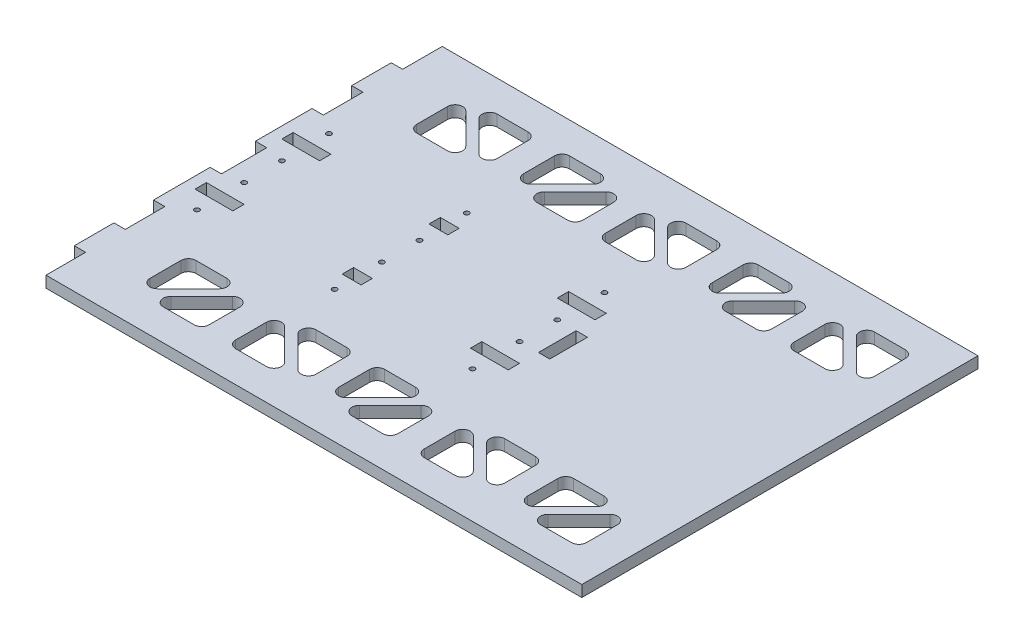
SolidWorks part; units mm, degrees
material "Balsa"
ref_plane "Front Plane" through (0, 0, 0) normal (0, 0, 1) x (1, 0, 0)
ref_plane "Top Plane" through (0, 0, 0) normal (0, 1, 0) x (1, 0, 0)
ref_plane "Right Plane" through (0, 0, 0) normal (1, 0, 0) x (0, 0, -1)
sketch "Sketch1" plane through (0, 0, 0) normal (0, 1, 0) x (1, 0, 0)
  line L0 (0, 0) -> (0, 105) construction
  line L1 (-145, 105) -> (145, 105)
  line L2 (-145, 105) -> (-145, -105)
  line L3 (-145, -105) -> (145, -105)
  line L4 (145, 105) -> (145, -105)
  line L5 (0, 0) -> (145, 0) construction
  dimension "D1" = 290
  dimension "D2" = 210
extrude "Boss-Extrude1" add sketch "Sketch1" along normal blind 6
sketch "Sketch2" plane through (0, 6, 0) normal (0, 1, 0) x (1, 0, 0)
  line L0 (-145, 105) -> (-145, -105) construction
  line L1 (145, 105) -> (-145, 105) construction
  line L2 (-145, 84) -> (-139, 84)
  line L3 (-145, 84) -> (-145, 105)
  line L4 (-145, 105) -> (-139, 105)
  line L6 (-139, 84) -> (-139, 105)
  line L7 (-145, -12) -> (-145, 0)
  line L8 (-145, 63) -> (-139, 63)
  line L9 (-145, 63) -> (-145, 42)
  line L10 (0, 0) -> (-139, 0) construction
  line L11 (-145, 42) -> (-139, 42)
  line L12 (-139, 63) -> (-139, 42)
  line L13 (-145, 12) -> (-139, 12)
  line L14 (-145, 12) -> (-145, 0)
  line L16 (-139, 12) -> (-139, -12)
  line L17 (-145, -12) -> (-139, -12)
  line L18 (-139, -63) -> (-139, -42)
  line L19 (-145, -42) -> (-139, -42)
  line L20 (-145, -63) -> (-145, -42)
  line L21 (-145, -63) -> (-139, -63)
  line L22 (-139, -84) -> (-139, -105)
  line L23 (-145, -105) -> (-139, -105)
  line L24 (-145, -84) -> (-145, -105)
  line L25 (-145, -84) -> (-139, -84)
  dimension "D1" = 21
  dimension "D2" = 21
  dimension "D3" = 30
  dimension "D4" = 6
  dimension "D5" = 21
extrude "Cut-Extrude1" cut sketch "Sketch2" against normal through all
sketch "Sketch3" plane through (0, 6, 0) normal (0, 1, 0) x (1, 0, 0)
  line L0 (0, 0) -> (-139, 0) construction
  line L1 (-139, 26) -> (-119, 26)
  line L2 (-139, 26) -> (-139, 20)
  line L3 (-139, 20) -> (-119, 20)
  line L4 (-119, 26) -> (-119, 20)
  line L5 (-61, 26) -> (-51, 26)
  line L6 (-61, 26) -> (-61, 20)
  line L7 (-61, 20) -> (-51, 20)
  line L8 (-51, 26) -> (-51, 20)
  line L9 (7, 26) -> (27, 26)
  line L10 (7, 26) -> (7, 20)
  line L11 (7, 20) -> (27, 20)
  line L12 (27, 26) -> (27, 20)
  line L13 (-139, -12) -> (-139, 12) construction
  line L14 (27, -26) -> (27, -20)
  line L15 (7, -20) -> (27, -20)
  line L16 (7, -26) -> (7, -20)
  line L17 (7, -26) -> (27, -26)
  line L18 (-51, -26) -> (-51, -20)
  line L19 (-61, -20) -> (-51, -20)
  line L20 (-61, -26) -> (-61, -20)
  line L21 (-61, -26) -> (-51, -26)
  line L22 (-119, -26) -> (-119, -20)
  line L23 (-139, -20) -> (-119, -20)
  line L24 (-139, -26) -> (-139, -20)
  line L25 (-139, -26) -> (-119, -26)
  point P21 (0, 0)
  dimension "D1" = 20
  dimension "D2" = 20
extrude "Cut-Extrude2" cut sketch "Sketch3" against normal through all
sketch "Sketch4" plane through (0, 6, 0) normal (0, 1, 0) x (1, 0, 0)
  line L1 (27, 10) -> (33, 10)
  line L2 (27, 10) -> (27, -10)
  line L3 (27, -10) -> (33, -10)
  line L4 (33, 10) -> (33, -10)
extrude "Cut-Extrude3" cut sketch "Sketch4" against normal through all
sketch "Sketch6" plane through (0, 6, 0) normal (0, 1, 0) x (1, 0, 0)
  circle A0 centre (-129, 35) radius 1.3
  circle A1 centre (-56, 35) radius 1.3
  circle A4 centre (17, 35) radius 1.3
  circle A6 centre (17, -35) radius 1.3
  circle A8 centre (-56, -35) radius 1.3
  circle A10 centre (-129, -35) radius 1.3
  dimension "D1" = 2.6
extrude "Cut-Extrude4" cut sketch "Sketch6" against normal through all
sketch "Sketch7" plane through (0, 6, 0) normal (0, 1, 0) x (1, 0, 0)
  line L0 (-110, 88.5) -> (-110, 58.5)
  line L1 (-110, 58.5) -> (-80, 58.5)
  line L2 (-80, 58.5) -> (-110, 88.5)
  line L3 (-103, 88.5) -> (-73, 58.5)
  line L4 (-73, 58.5) -> (-73, 88.5)
  line L5 (-73, 88.5) -> (-103, 88.5)
  line L6 (-145, 73.5) -> (145, 73.5) construction
  line L7 (-145, 84) -> (-145, 63) construction
  line L8 (145, -105) -> (145, 105) construction
  line L9 (-110, 73.5) -> (-73, 73.5) construction
  line L10 (-66, 105) -> (-66, -105) construction
  line L11 (145, 105) -> (-139, 105) construction
  line L12 (-139, -105) -> (145, -105) construction
  line L13 (-59, 88.5) -> (-29, 88.5)
  line L14 (-59, 58.5) -> (-59, 88.5)
  line L15 (-29, 88.5) -> (-59, 58.5)
  line L16 (-22, 58.5) -> (-52, 58.5)
  line L17 (-52, 58.5) -> (-22, 88.5)
  line L18 (-22, 88.5) -> (-22, 58.5)
  line L19 (-10, 88.5) -> (-10, 58.5)
  line L20 (-10, 58.5) -> (20, 58.5)
  line L21 (20, 58.5) -> (-10, 88.5)
  line L22 (-3, 88.5) -> (27, 58.5)
  line L23 (27, 58.5) -> (27, 88.5)
  line L24 (27, 88.5) -> (-3, 88.5)
  line L25 (41, 88.5) -> (71, 88.5)
  line L26 (41, 58.5) -> (41, 88.5)
  line L27 (71, 88.5) -> (41, 58.5)
  line L28 (78, 58.5) -> (48, 58.5)
  line L29 (48, 58.5) -> (78, 88.5)
  line L30 (78, 88.5) -> (78, 58.5)
  line L31 (-10, 73.5) -> (27, 73.5) construction
  line L32 (90, 88.5) -> (90, 58.5)
  line L33 (90, 58.5) -> (120, 58.5)
  line L34 (120, 58.5) -> (90, 88.5)
  line L35 (97, 88.5) -> (127, 58.5)
  line L36 (127, 58.5) -> (127, 88.5)
  line L37 (127, 88.5) -> (97, 88.5)
  line L38 (-139, 0) -> (145, 0) construction
  line L39 (-139, -12) -> (-139, 12) construction
  line L43 (-145, -73.5) -> (145, -73.5) construction
  line L44 (90, 73.5) -> (127, 73.5) construction
  line L45 (171, 88.5) -> (141, 58.5) [skipped]
  line L46 (178, 58.5) -> (148, 58.5) [skipped]
  line L47 (148, 58.5) -> (178, 88.5) [skipped]
  line L48 (178, 88.5) -> (178, 58.5) [skipped]
  line L49 (141, 88.5) -> (171, 88.5) [skipped]
  line L50 (141, 58.5) -> (141, 88.5) [skipped]
  dimension "D1" = 30
  dimension "D2" = 35
  dimension "D3" = 7
  dimension "D4" = 7
  dimension "D5" = 3
extrude "Cut-Extrude5" cut sketch "Sketch7" against normal through all
fillet "Fillet1" radius 4 30 edges at (97, 3, -88.5) (127, 3, -88.5) (127, 3, -58.5) (120, 3, -58.5) (90, 3, -88.5) (90, 3, -58.5) (78, 3, -58.5) (78, 3, -88.5) (48, 3, -58.5) (41, 3, -58.5) (71, 3, -88.5) (41, 3, -88.5) (-3, 3, -88.5) (27, 3, -88.5) (27, 3, -58.5) (-10, 3, -58.5) (20, 3, -58.5) (-10, 3, -88.5) (-52, 3, -58.5) (-22, 3, -58.5) (-22, 3, -88.5) (-29, 3, -88.5) (-59, 3, -88.5) (-59, 3, -58.5) (-73, 3, -58.5) (-73, 3, -88.5) (-103, 3, -88.5) (-110, 3, -58.5) (-80, 3, -58.5) (-110, 3, -88.5)
mirror "Mirror1" about plane through (0, 0, 0) normal (0, 0, 1) of "Fillet1", "Cut-Extrude5"
sketch "Sketch8" plane through (0, 6, 0) normal (0, 1, 0) x (1, 0, 0)
  line L0 (-139, 0) -> (145, 0) construction
  line L1 (-139, -12) -> (-139, 12) construction
  line L2 (145, -105) -> (145, 105) construction
  circle A0 centre (-129, -10) radius 1.3
  circle A2 centre (-56, -10) radius 1.3
  circle A4 centre (17, -10) radius 1.3
  circle A6 centre (-129, 10) radius 1.3
  circle A7 centre (-56, 10) radius 1.3
  circle A8 centre (17, 10) radius 1.3
  dimension "D1" = 2.6
extrude "Cut-Extrude6" cut sketch "Sketch8" against normal through all
